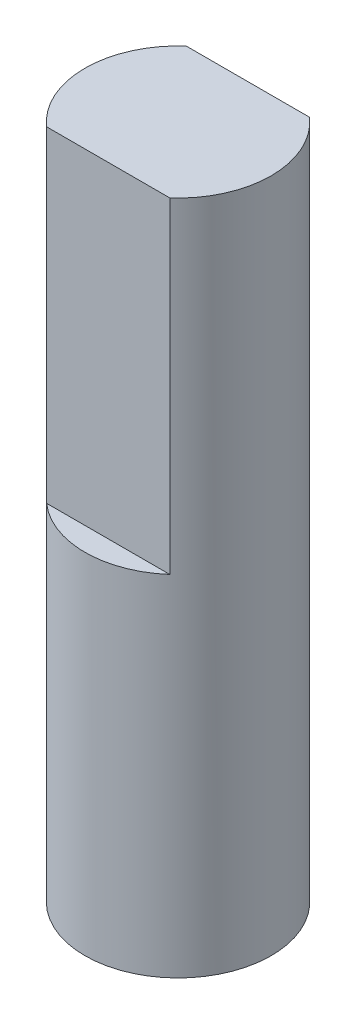
SolidWorks part; units mm, degrees
ref_plane "Alzado" through (0, 0, 0) normal (0, 0, 1) x (1, 0, 0)
ref_plane "Planta" through (0, 0, 0) normal (0, 1, 0) x (1, 0, 0)
ref_plane "Vista lateral" through (0, 0, 0) normal (1, 0, 0) x (0, 0, -1)
sketch "Croquis1" plane through (0, 0, 0) normal (0, 1, 0) x (1, 0, 0)
  circle A2 centre (0, 0) radius 4
  dimension "D1" = 8
extrude "Saliente-Extruir1" add sketch "Croquis1" along normal blind 15
sketch "Croquis2" plane through (0, 15, 0) normal (0, 1, 0) x (1, 0, 0)
  line L1 (-2.6458, -3) -> (2.6458, -3)
  line L3 (-2.6458, 3) -> (2.6458, 3)
  line L5 (-3.4581, -2.0104) -> (3.4581, 2.0104) construction
  line L6 (-3.4581, 2.0104) -> (3.4581, -2.0104) construction
  arc A0 (2.6458, -3) -> (2.6458, 3) centre (0, 0) ccw
  arc A1 (-2.6458, 3) -> (-2.6458, -3) centre (0, 0) ccw
extrude "Saliente-Extruir2" add sketch "Croquis2" along normal blind 14
